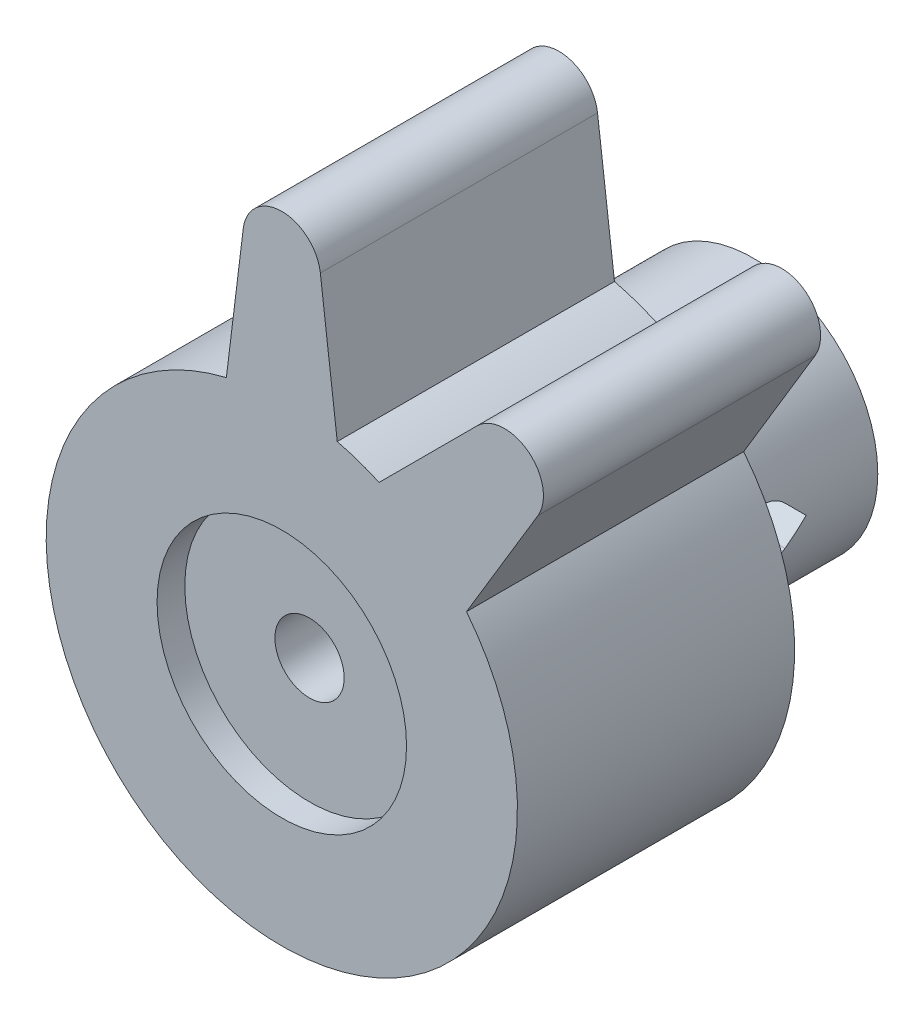
SolidWorks part; units mm, degrees
ref_plane "Front Plane" through (0, 0, 0) normal (0, 0, 1) x (1, 0, 0)
ref_plane "Top Plane" through (0, 0, 0) normal (0, 1, 0) x (1, 0, 0)
ref_plane "Right Plane" through (0, 0, 0) normal (1, 0, 0) x (0, 0, -1)
sketch "Sketch1" plane through (0, 0, 0) normal (0, 0, 1) x (1, 0, 0)
  line L0 (0, 0) -> (0, 51.188) construction
  line L1 (-2, 8.2614) -> (-1.3907, 13.2241)
  line L2 (2, 8.2614) -> (1.3907, 13.2241)
  line L3 (0, 0) -> (22.4184, 65.1077) construction
  line L4 (6.6622, 5.2787) -> (9.2374, 9.5646)
  line L5 (0, 0) -> (31.5145, 40.3367) construction
  line L6 (3.5102, 7.7414) -> (7.0457, 11.2769)
  circle A0 centre (0, 0) radius 8.5
  circle A1 centre (0, 0) radius 1.25
  arc A2 (-1.3907, 13.2241) -> (1.3907, 13.2241) centre (0, 13.0533) cw
  arc A3 (9.2374, 9.5646) -> (7.0457, 11.2769) centre (8.0364, 10.2862) ccw
  circle A4 centre (0, 0) radius 12 construction
  dimension "D1" = 24
  dimension "D2" = 17
  dimension "D3" = 2.5
  dimension "D4" = 7
  dimension "D7" = 5
  dimension "D5" = 4
  dimension "D6" = 19
extrude "Boss-Extrude1" add sketch "Sketch1" along normal blind 10 contours A0 A1 | A2 L1 A0 L2 | A0 region at (0, 11.1065, 0) region at (0, 8.2596, 0) region at (6.8378, 8.752, 0)
sketch "Sketch5" plane through (0, 0, 0) normal (0, 0, -1) x (-1, 0, 0)
  circle A0 centre (0, 0) radius 3
  circle A1 centre (0, 0) radius 4.5
  dimension "D1" = 9
  dimension "D2" = 6
extrude "Boss-Extrude3" add sketch "Sketch5" along normal blind 7
sketch "Sketch6" plane through (0, 0, 0) normal (1, 0, 0) x (0, 0, -1)
  line L0 (3.7071, -0.7071) -> (4.4142, 0)
  line L1 (4.4142, 0) -> (3.7071, 0.7071)
  line L2 (7, 0) -> (0, 0) construction
  circle A0 centre (3, 0) radius 1
  point P5 (0, 0)
  point P7 (0, 0)
  point P8 (0, 0)
  dimension "D1" = 2
  dimension "D2" = 3
sketch "Sketch8" plane through (0, 0, 10) normal (0, 0, 1) x (1, 0, 0)
  circle A0 centre (0, 0) radius 4.5
  dimension "D1" = 9
extrude "Cut-Extrude2" cut sketch "Sketch8" against normal blind 1
extrude "Cut-Extrude3" cut sketch "Sketch6" against normal through all both and the other way through all contours A0 | A0 L0 L1 region at (0, 0, -4.0983) region at (0, 0, -3)
